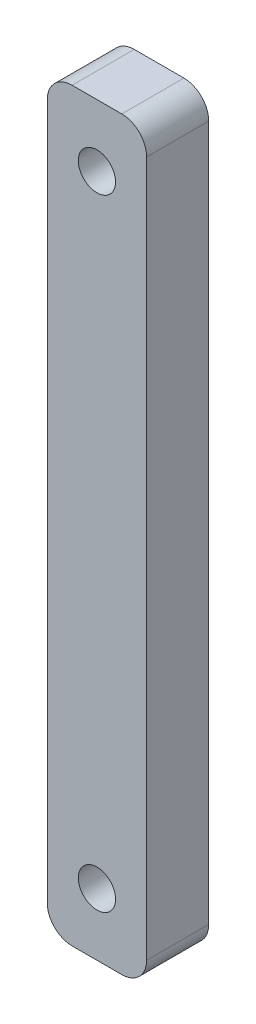
SolidWorks part; units mm, degrees
ref_plane "前视基准面" through (0, 0, 0) normal (0, 0, 1) x (1, 0, 0)
ref_plane "上视基准面" through (0, 0, 0) normal (0, 1, 0) x (1, 0, 0)
ref_plane "右视基准面" through (0, 0, 0) normal (1, 0, 0) x (0, 0, -1)
sketch "草图1" plane through (0, 0, 0) normal (0, 0, 1) x (1, 0, 0)
  line L1 (4, -30) -> (-4, -30)
  line L2 (4, -30) -> (4, 30)
  line L3 (4, 30) -> (-4, 30)
  line L4 (-4, -30) -> (-4, 30)
  line L5 (4, -30) -> (-4, 30) construction
  line L6 (4, 30) -> (-4, -30) construction
  point P0 (0, 0)
  dimension "D1" = 8
  dimension "D2" = 60
extrude "凸台-拉伸1" add sketch "草图1" along normal blind 5
sketch "草图2" plane through (0, 0, 5) normal (0, 0, 1) x (1, 0, 0)
  line L0 (0, -30) -> (0, -25) construction
  line L1 (-4, -30) -> (4, -30) construction
  line L2 (0, 30) -> (0, 25) construction
  line L3 (4, 30) -> (-4, 30) construction
  circle A0 centre (0, 25) radius 1.5
  circle A1 centre (0, -25) radius 1.5
  dimension "D3" = 3
  dimension "D4" = 3
  dimension "D1" = 5
  dimension "D2" = 5
extrude "切除-拉伸1" cut sketch "草图2" against normal through all
fillet "圆角1" radius 2 4 edges at (-4, -30, 2.5) (4, -30, 2.5) (4, 30, 2.5) (-4, 30, 2.5)
